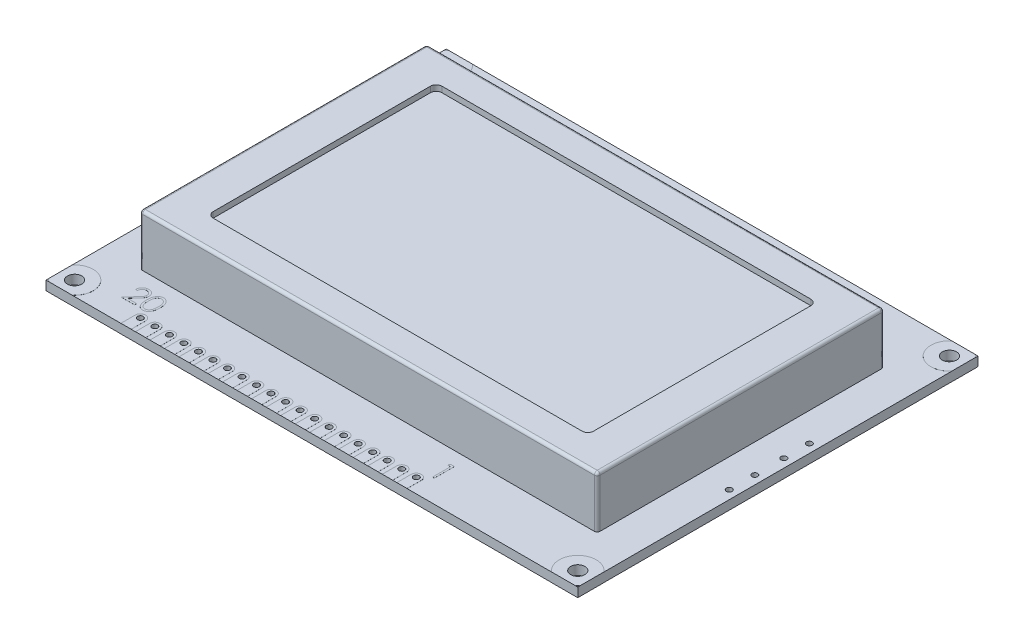
SolidWorks part; units mm, degrees
material "A-Glass Fiber"
ref_plane "Front Plane" through (0, 0, 0) normal (0, 0, 1) x (1, 0, 0)
ref_plane "Top Plane" through (0, 0, 0) normal (0, 1, 0) x (1, 0, 0)
ref_plane "Right Plane" through (0, 0, 0) normal (1, 0, 0) x (0, 0, -1)
sketch "Sketch1" plane through (0, 0, 0) normal (0, 1, 0) x (1, 0, 0)
  line L0 (2.5, 67.5) -> (90.5, 67.5) construction
  line L1 (0, 0) -> (93, 0)
  line L2 (0, 0) -> (0, 70)
  line L3 (0, 70) -> (93, 70)
  line L4 (93, 0) -> (93, 70)
  line L5 (2.5, 2.5) -> (90.5, 2.5) construction
  line L6 (90.5, 2.5) -> (90.5, 67.5) construction
  line L7 (2.5, 67.5) -> (2.5, 2.5) construction
  line L8 (90.5, 35) -> (91.5, 35) construction
  line L9 (91.5, 37.54) -> (91.5, 32.46) construction
  line L10 (91.5, 37.54) -> (91.5, 42) construction
  line L11 (91.5, 32.46) -> (91.5, 28) construction
  circle A0 centre (2.5, 67.5) radius 1.25
  circle A1 centre (90.5, 67.5) radius 1.25
  circle A2 centre (90.5, 2.5) radius 1.25
  circle A3 centre (2.5, 2.5) radius 1.25
  circle A4 centre (14, 2.5) radius 0.5
  circle A5 centre (16.54, 2.5) radius 0.5
  circle A6 centre (19.08, 2.5) radius 0.5
  circle A7 centre (21.62, 2.5) radius 0.5
  circle A8 centre (24.16, 2.5) radius 0.5
  circle A9 centre (26.7, 2.5) radius 0.5
  circle A10 centre (29.24, 2.5) radius 0.5
  circle A11 centre (31.78, 2.5) radius 0.5
  circle A12 centre (34.32, 2.5) radius 0.5
  circle A13 centre (36.86, 2.5) radius 0.5
  circle A14 centre (39.4, 2.5) radius 0.5
  circle A15 centre (41.94, 2.5) radius 0.5
  circle A16 centre (44.48, 2.5) radius 0.5
  circle A17 centre (47.02, 2.5) radius 0.5
  circle A18 centre (49.56, 2.5) radius 0.5
  circle A19 centre (52.1, 2.5) radius 0.5
  circle A20 centre (54.64, 2.5) radius 0.5
  circle A21 centre (57.18, 2.5) radius 0.5
  circle A22 centre (59.72, 2.5) radius 0.5
  circle A23 centre (62.26, 2.5) radius 0.5
  circle A24 centre (91.5, 42) radius 0.5
  circle A25 centre (91.5, 37.54) radius 0.5
  circle A26 centre (91.5, 32.46) radius 0.5
  circle A27 centre (91.5, 28) radius 0.5
  point P57 (91.5, 35)
  dimension "D3" = 2.5
  dimension "D9" = 1
  dimension "D13" = 1
  dimension "D1" = 93
  dimension "D2" = 70
  dimension "D4" = 2.5
  dimension "D5" = 2.5
  dimension "D6" = 2.5
  dimension "D7" = 2.5
  dimension "D8" = 14
  dimension "D11" = 5.08
  dimension "D12" = 14
  dimension "D14" = 1.5
  dimension "D10" = 20
extrude "Boss-Extrude1" add sketch "Sketch1" along normal blind 1.6
sketch "Sketch4" plane through (0, 0, 0) normal (0, 1, 0) x (1, 0, 0)
  line L0 (13.1, 2.5) -> (13.1, 0)
  line L1 (0, 0) -> (93, 0) construction
  line L2 (13.1, 0) -> (14.9, 0)
  line L3 (14.9, 0) -> (14.9, 2.5)
  line L4 (15.64, 2.5) -> (15.64, 0)
  line L5 (15.64, 0) -> (17.44, 0)
  line L6 (17.44, 0) -> (17.44, 2.5)
  line L7 (18.18, 2.5) -> (18.18, 0)
  line L8 (18.18, 0) -> (19.98, 0)
  line L9 (19.98, 0) -> (19.98, 2.5)
  line L10 (20.72, 2.5) -> (20.72, 0)
  line L11 (20.72, 0) -> (22.52, 0)
  line L12 (22.52, 0) -> (22.52, 2.5)
  line L13 (23.26, 2.5) -> (23.26, 0)
  line L14 (23.26, 0) -> (25.06, 0)
  line L15 (25.06, 0) -> (25.06, 2.5)
  line L16 (25.8, 2.5) -> (25.8, 0)
  line L17 (25.8, 0) -> (27.6, 0)
  line L18 (27.6, 0) -> (27.6, 2.5)
  line L19 (28.34, 2.5) -> (28.34, 0)
  line L20 (28.34, 0) -> (30.14, 0)
  line L21 (30.14, 0) -> (30.14, 2.5)
  line L22 (30.88, 2.5) -> (30.88, 0)
  line L23 (30.88, 0) -> (32.68, 0)
  line L24 (32.68, 0) -> (32.68, 2.5)
  line L25 (33.42, 2.5) -> (33.42, 0)
  line L26 (33.42, 0) -> (35.22, 0)
  line L27 (35.22, 0) -> (35.22, 2.5)
  line L28 (35.96, 2.5) -> (35.96, 0)
  line L29 (35.96, 0) -> (37.76, 0)
  line L30 (37.76, 0) -> (37.76, 2.5)
  line L31 (38.5, 2.5) -> (38.5, 0)
  line L32 (38.5, 0) -> (40.3, 0)
  line L33 (40.3, 0) -> (40.3, 2.5)
  line L34 (41.04, 2.5) -> (41.04, 0)
  line L35 (41.04, 0) -> (42.84, 0)
  line L36 (42.84, 0) -> (42.84, 2.5)
  line L37 (43.58, 2.5) -> (43.58, 0)
  line L38 (43.58, 0) -> (45.38, 0)
  line L39 (45.38, 0) -> (45.38, 2.5)
  line L40 (46.12, 2.5) -> (46.12, 0)
  line L41 (46.12, 0) -> (47.92, 0)
  line L42 (47.92, 0) -> (47.92, 2.5)
  line L43 (48.66, 2.5) -> (48.66, 0)
  line L44 (48.66, 0) -> (50.46, 0)
  line L45 (50.46, 0) -> (50.46, 2.5)
  line L46 (51.2, 2.5) -> (51.2, 0)
  line L47 (51.2, 0) -> (53, 0)
  line L48 (53, 0) -> (53, 2.5)
  line L49 (53.74, 2.5) -> (53.74, 0)
  line L50 (53.74, 0) -> (55.54, 0)
  line L51 (55.54, 0) -> (55.54, 2.5)
  line L52 (56.28, 2.5) -> (56.28, 0)
  line L53 (56.28, 0) -> (58.08, 0)
  line L54 (58.08, 0) -> (58.08, 2.5)
  line L55 (58.82, 2.5) -> (58.82, 0)
  line L56 (58.82, 0) -> (60.62, 0)
  line L57 (60.62, 0) -> (60.62, 2.5)
  line L58 (61.36, 2.5) -> (61.36, 0)
  line L59 (61.36, 0) -> (63.16, 0)
  line L60 (63.16, 0) -> (63.16, 2.5)
  line L61 (0, 4.5767) -> (0, 0.4233)
  line L62 (0, 70) -> (0, 0) construction
  line L63 (0.4233, 0) -> (4.5767, 0)
  line L64 (4.5767, 70) -> (0.4233, 70)
  line L65 (93, 70) -> (0, 70) construction
  line L66 (0, 69.5767) -> (0, 65.4233)
  line L67 (88.4233, 70) -> (92.5767, 70)
  line L68 (93, 69.5767) -> (93, 65.4233)
  line L69 (93, 0) -> (93, 70) construction
  line L70 (88.4233, 0) -> (92.5767, 0)
  line L71 (93, 4.5767) -> (93, 0.4233)
  arc A0 (13.1, 2.5) -> (14.9, 2.5) centre (14, 2.5) cw
  circle A1 centre (14, 2.5) radius 0.5
  arc A2 (15.64, 2.5) -> (17.44, 2.5) centre (16.54, 2.5) cw
  circle A3 centre (16.54, 2.5) radius 0.5
  arc A4 (18.18, 2.5) -> (19.98, 2.5) centre (19.08, 2.5) cw
  circle A5 centre (19.08, 2.5) radius 0.5
  arc A6 (20.72, 2.5) -> (22.52, 2.5) centre (21.62, 2.5) cw
  circle A7 centre (21.62, 2.5) radius 0.5
  arc A8 (23.26, 2.5) -> (25.06, 2.5) centre (24.16, 2.5) cw
  circle A9 centre (24.16, 2.5) radius 0.5
  arc A10 (25.8, 2.5) -> (27.6, 2.5) centre (26.7, 2.5) cw
  circle A11 centre (26.7, 2.5) radius 0.5
  arc A12 (28.34, 2.5) -> (30.14, 2.5) centre (29.24, 2.5) cw
  circle A13 centre (29.24, 2.5) radius 0.5
  arc A14 (30.88, 2.5) -> (32.68, 2.5) centre (31.78, 2.5) cw
  circle A15 centre (31.78, 2.5) radius 0.5
  arc A16 (33.42, 2.5) -> (35.22, 2.5) centre (34.32, 2.5) cw
  circle A17 centre (34.32, 2.5) radius 0.5
  arc A18 (35.96, 2.5) -> (37.76, 2.5) centre (36.86, 2.5) cw
  circle A19 centre (36.86, 2.5) radius 0.5
  arc A20 (38.5, 2.5) -> (40.3, 2.5) centre (39.4, 2.5) cw
  circle A21 centre (39.4, 2.5) radius 0.5
  arc A22 (41.04, 2.5) -> (42.84, 2.5) centre (41.94, 2.5) cw
  circle A23 centre (41.94, 2.5) radius 0.5
  arc A24 (43.58, 2.5) -> (45.38, 2.5) centre (44.48, 2.5) cw
  circle A25 centre (44.48, 2.5) radius 0.5
  arc A26 (46.12, 2.5) -> (47.92, 2.5) centre (47.02, 2.5) cw
  circle A27 centre (47.02, 2.5) radius 0.5
  arc A28 (48.66, 2.5) -> (50.46, 2.5) centre (49.56, 2.5) cw
  circle A29 centre (49.56, 2.5) radius 0.5
  arc A30 (51.2, 2.5) -> (53, 2.5) centre (52.1, 2.5) cw
  circle A31 centre (52.1, 2.5) radius 0.5
  arc A32 (53.74, 2.5) -> (55.54, 2.5) centre (54.64, 2.5) cw
  circle A33 centre (54.64, 2.5) radius 0.5
  arc A34 (56.28, 2.5) -> (58.08, 2.5) centre (57.18, 2.5) cw
  circle A35 centre (57.18, 2.5) radius 0.5
  arc A36 (58.82, 2.5) -> (60.62, 2.5) centre (59.72, 2.5) cw
  circle A37 centre (59.72, 2.5) radius 0.5
  arc A38 (61.36, 2.5) -> (63.16, 2.5) centre (62.26, 2.5) cw
  circle A39 centre (62.26, 2.5) radius 0.5
  arc A40 (0, 0.4233) -> (0.4233, 0) centre (2.5, 2.5) ccw
  circle A41 centre (2.5, 2.5) radius 1.25
  circle A42 centre (90.5, 67.5) radius 1.25
  arc A43 (88.4233, 70) -> (93, 65.4233) centre (90.5, 67.5) ccw
  circle A44 centre (2.5, 67.5) radius 1.25
  arc A45 (0.4233, 70) -> (0, 69.5767) centre (2.5, 67.5) ccw
  circle A46 centre (90.5, 2.5) radius 1.25
  arc A47 (93, 4.5767) -> (88.4233, 0) centre (90.5, 2.5) ccw
  arc A48 (4.5767, 0) -> (0, 4.5767) centre (2.5, 2.5) ccw
  arc A49 (0, 65.4233) -> (4.5767, 70) centre (2.5, 67.5) ccw
  arc A50 (93, 69.5767) -> (92.5767, 70) centre (90.5, 67.5) ccw
  arc A51 (92.5767, 0) -> (93, 0.4233) centre (90.5, 2.5) ccw
  dimension "D1" = 20
  dimension "D2" = 0.9
  dimension "D3" = 6.5
extrude "Boss-Extrude2" add sketch "Sketch4" along normal blind 1.61 and the other way blind 0.01
sketch "Sketch5" plane through (0, 0, 0) normal (0, 1, 0) x (1, 0, 0)
  line L0 (0, 70) -> (93, 0) construction
  line L2 (6.5, 60.1) -> (86.5, 60.1)
  line L3 (6.5, 60.1) -> (6.5, 9.9)
  line L4 (6.5, 9.9) -> (86.5, 9.9)
  line L5 (86.5, 60.1) -> (86.5, 9.9)
  line L6 (6.5, 60.1) -> (86.5, 9.9) construction
  line L7 (6.5, 9.9) -> (86.5, 60.1) construction
  point P4 (46.5, 35)
  dimension "D1" = 50.2
  dimension "D2" = 80
extrude "Boss-Extrude3" add sketch "Sketch5" along normal blind 9 from surface starting at face at (91.5, 1.6, -27.5)
fillet "Fillet1" radius 0.5 8 edges at (86.5, 6.1, -9.9) (86.5, 6.1, -60.1) (86.5, 10.6, -35) (46.5, 10.6, -60.1) (6.5, 6.1, -60.1) (46.5, 10.6, -9.9) (6.5, 10.6, -35) (6.5, 6.1, -9.9)
sketch "Sketch6" plane through (0, 0, 0) normal (0, 1, 0) x (1, 0, 0)
  line L0 (0, 70) -> (93, 0) construction
  line L2 (14.24, 55) -> (78.76, 55)
  line L3 (13.24, 54) -> (13.24, 16)
  line L4 (14.24, 15) -> (78.76, 15)
  line L5 (79.76, 54) -> (79.76, 16)
  line L6 (13.24, 55) -> (79.76, 15) construction
  line L7 (13.24, 15) -> (79.76, 55) construction
  arc A0 (78.76, 55) -> (79.76, 54) centre (78.76, 54) cw
  arc A1 (78.76, 15) -> (79.76, 16) centre (78.76, 16) ccw
  arc A2 (13.24, 16) -> (14.24, 15) centre (14.24, 16) ccw
  arc A3 (14.24, 55) -> (13.24, 54) centre (14.24, 54) ccw
  point P4 (46.5, 35)
  dimension "D3" = 1
  dimension "D1" = 66.52
  dimension "D2" = 40
extrude "Cut-Extrude1" cut sketch "Sketch6" against normal blind 1 from surface starting at face at (46.5, 10.6, -35)
sketch "Sketch7" plane through (0, 0, 0) normal (0, 1, 0) x (1, 0, 0)
  text T0 "1"
  text T1 "20"
extrude "Boss-Extrude4" add sketch "Sketch7" along normal blind 0.01 from surface starting at face at (38.8909, 1.6, -4.5227)
sketch "Sketch8" plane through (0, 0, 0) normal (0, 1, 0) x (1, 0, 0)
  circle A0 centre (19.3751, 34.1638) radius 7.5
  circle A1 centre (38.6082, 39.2856) radius 7.5
  circle A2 centre (59.3046, 35.4181) radius 7.5
  dimension "D1" = 15
extrude "Boss-Extrude5" add sketch "Sketch8" against normal blind 3
fillet "Fillet2" radius 9 3 edges at (59.3046, -3, -27.9181) (38.6082, -3, -31.7856) (19.3751, -3, -26.6638)
